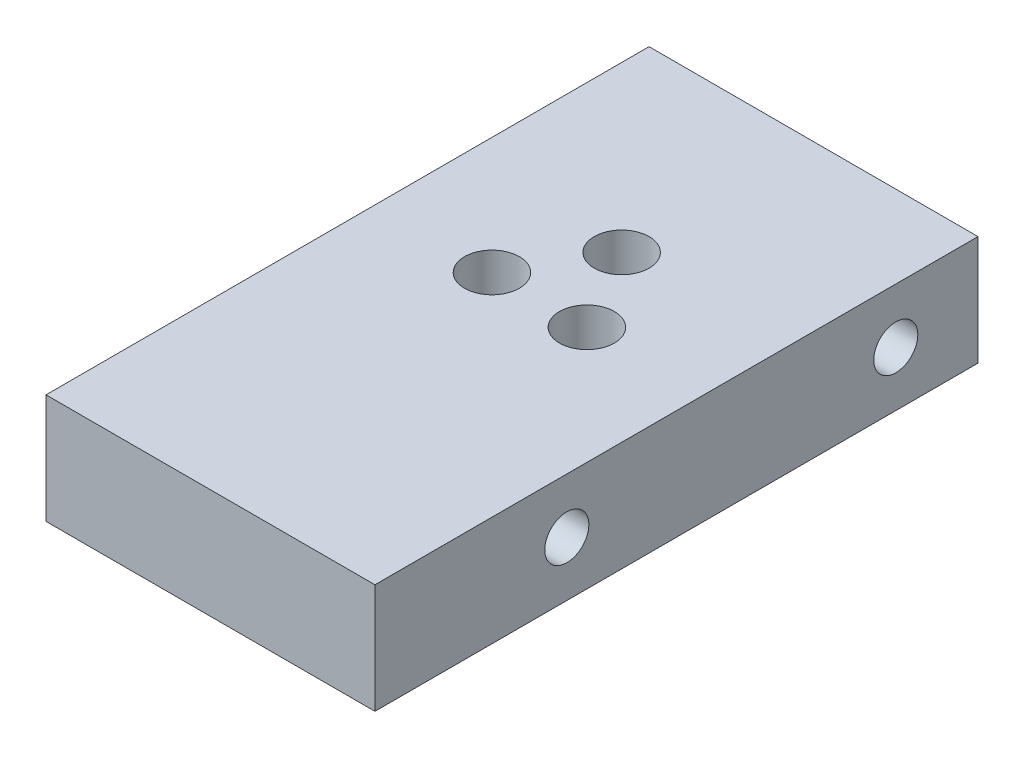
SolidWorks part; units mm, degrees
material "6061 Alloy"
ref_plane "Front Plane" through (0, 0, 0) normal (0, 0, 1) x (1, 0, 0)
ref_plane "Top Plane" through (0, 0, 0) normal (0, 1, 0) x (1, 0, 0)
ref_plane "Right Plane" through (0, 0, 0) normal (1, 0, 0) x (0, 0, -1)
sketch "Sketch1" plane through (0, 0, 0) normal (0, 1, 0) x (1, 0, 0)
  line L1 (-19.05, 34.925) -> (19.05, 34.925)
  line L2 (-19.05, 34.925) -> (-19.05, -34.925)
  line L3 (-19.05, -34.925) -> (19.05, -34.925)
  line L4 (19.05, 34.925) -> (19.05, -34.925)
  line L5 (-19.05, 34.925) -> (19.05, -34.925) construction
  line L6 (-19.05, -34.925) -> (19.05, 34.925) construction
  point P0 (0, 0)
  dimension "D1" = 69.85
  dimension "D2" = 38.1
extrude "Boss-Extrude1" add sketch "Sketch1" along normal blind 12.7
hole_wizard "1/4 (0.25) Diameter Hole1" positions "Sketch3" profile "Sketch2" hole size "1/4" standard "ANSI Inch"
sketch "Sketch3" plane through (0, 0, 0) normal (0, -1, 0) x (-1, 0, 0)
  line L0 (0, 34.925) -> (0, -22.225) construction
  line L1 (-19.05, 34.925) -> (19.05, 34.925) construction
  line L2 (0, 6.35) -> (19.05, 6.35) construction
  line L4 (19.05, 34.925) -> (19.05, -34.925) construction
  circle A0 centre (0, 6.35) radius 6.35
  point P4 (0, 12.7)
  point P21 (5.4993, 3.175)
  point P22 (-5.4993, 3.175)
  dimension "D1" = 57.15
  dimension "D3" = 6.35
  dimension "D2" = 3
sketch "Sketch2" plane through (0, 0, -12.7) normal (1, 0, 0) x (0, 0, -1)
  line L0 (0, 0) -> (0, 18.9257)
  line L1 (0, 18.9257) -> (3.175, 17.018)
  line L2 (3.175, 17.018) -> (3.175, 0)
  line L5 (3.175, 0) -> (0, 0)
  line L10 (0, 18.9257) -> (-3.175, 17.018) construction
  line L11 (0, -6.35) -> (0, 107.95) construction
  dimension "Hole Dia." = 6.35
  dimension "Hole Depth" = 17.018
  dimension "Drill Angle" = 118
hole_wizard "1/4-20 Tapped Hole1" positions "3DSketch1" profile "Sketch4" tap size "1/4-20" standard "ANSI Inch"
sketch3d "3DSketch1"
  line L4 (19.05, 6.35, -25.4) -> (19.05, 6.35, -34.925) construction
  line L5 (19.05, 12.7, -34.925) -> (19.05, 0, -34.925) construction
  line L7 (19.05, 6.35, 12.7) -> (19.05, 6.35, 22.225) construction
  line L9 (19.05, 12.7, 22.225) -> (19.05, 0, 22.225) construction
  line L10 (19.05, 12.7, 34.925) -> (19.05, 12.7, -34.925) construction
  line L11 (19.05, 0, 34.925) -> (19.05, 0, -34.925) construction
  point P0 (-19.05, 6.35, -25.4)
  point P2 (-19.05, 6.35, 12.7)
  point P4 (19.05, 6.35, 12.7)
  point P6 (19.05, 6.35, -25.4)
  dimension "D1" = 9.525
  dimension "D2" = 57.15
sketch "Sketch4" plane through (-19.05, 6.35, -25.4) normal (0, 1, 0) x (0, 0, 1)
  line L0 (0, 0) -> (0, 18.0438)
  line L1 (0, 18.0438) -> (2.5527, 16.51)
  line L2 (2.5527, 16.51) -> (2.5527, 0)
  line L5 (2.5527, 0) -> (0, 0)
  line L10 (0, 18.0438) -> (-2.5527, 16.51) construction
  line L11 (0, -6.35) -> (0, 107.95) construction
  dimension "Tap Drill Dia." = 5.1054
  dimension "Tap Drill Depth" = 16.51
  dimension "Drill Angle" = 118
sketch "Sketch5" plane through (0, 0, 0) normal (0, -1, 0) x (1, 0, 0)
  line L0 (10.9985, -6.35) -> (5.4993, -15.875)
  line L1 (-5.4993, -15.875) -> (-10.9985, -6.35)
  line L2 (-5.4993, 3.175) -> (5.4993, 3.175)
  arc A0 (5.4993, -15.875) -> (-5.4993, -15.875) centre (0, -12.7) cw
  arc A1 (-5.4993, 3.175) -> (-10.9985, -6.35) centre (-5.4993, -3.175) ccw
  arc A2 (5.4993, 3.175) -> (10.9985, -6.35) centre (5.4993, -3.175) cw
  dimension "D1" = 6.35
extrude "Cut-Extrude1" cut sketch "Sketch5" against normal blind 3.81
